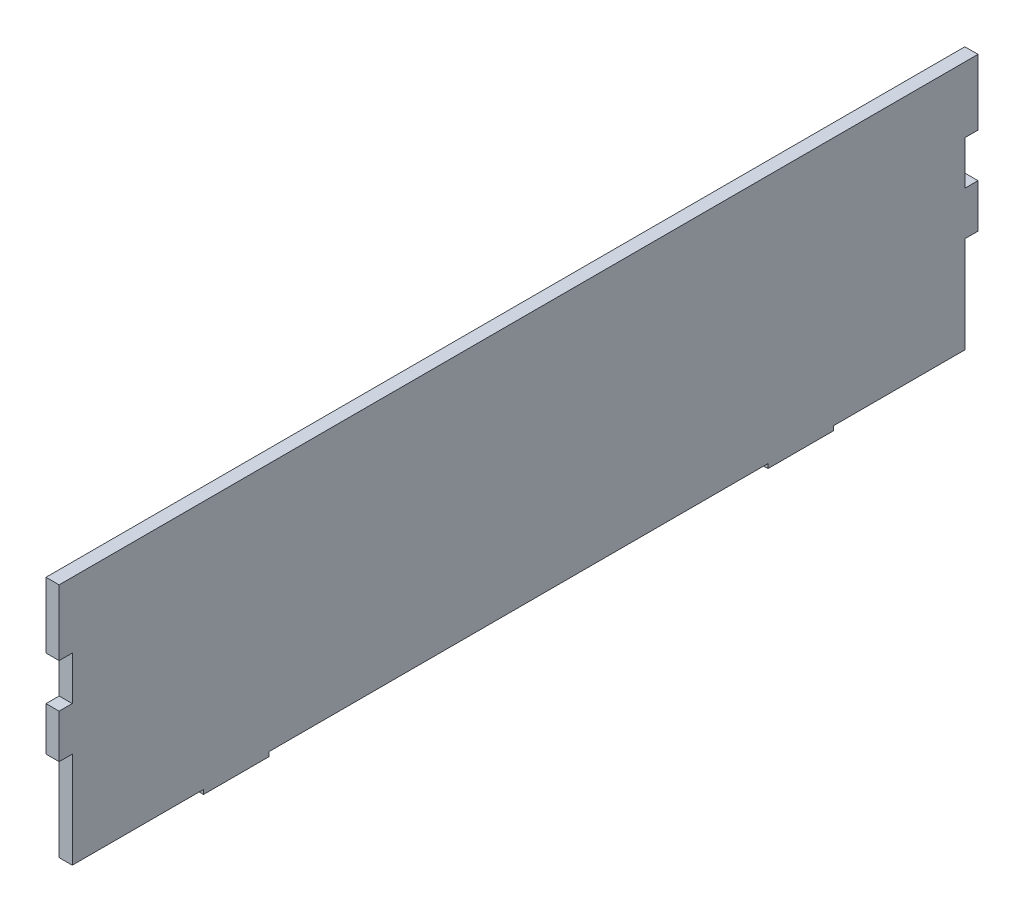
SolidWorks part; units mm, degrees
ref_plane "前视基准面" through (0, 0, 0) normal (0, 0, 1) x (1, 0, 0)
ref_plane "上视基准面" through (0, 0, 0) normal (0, 1, 0) x (1, 0, 0)
ref_plane "右视基准面" through (0, 0, 0) normal (1, 0, 0) x (0, 0, -1)
sketch "草图1" plane through (0, 0, 0) normal (0, 0, 1) x (1, 0, 0)
  line L0 (0, -1.0782) -> (0, -59.0782)
  line L1 (0, -59.0782) -> (150, -59.0782)
  line L3 (24.7207, -21.434) -> (24.7207, -1.0782)
  line L4 (24.7207, -1.0782) -> (0, -1.0782)
  line L5 (150, -59.0782) -> (150, -56.0782)
  line L6 (150, -56.0782) -> (24.7207, -21.434)
  dimension "D1" = 150
  dimension "D2" = 58
  dimension "D3" = 3
extrude "凸台-拉伸1" add sketch "草图1" along normal blind 0.5
sketch "草图2" plane through (0, 0, 0) normal (0, 0, -1) x (-1, 0, 0)
  line L0 (0, -1.0782) -> (-3, -1.0782)
  line L1 (-24.7207, -1.0782) -> (0, -1.0782) construction
  line L2 (-3, -1.0782) -> (-3, -54.0782)
  line L4 (-149.75, -59.0782) -> (0, -59.0782)
  line L5 (0, -59.0782) -> (0, -1.0782)
  line L6 (-150, -58.8282) -> (-150, -58.8207)
  line L7 (-149.7576, -58.5708) -> (-3, -54.0782)
  arc A0 (-150, -58.8207) -> (-149.7576, -58.5708) centre (-149.75, -58.8207) cw
  arc A1 (-150, -58.8282) -> (-149.75, -59.0782) centre (-149.75, -58.8282) ccw
  point P14 (-150, -58.5782)
  point P17 (-150, -59.0782)
  dimension "D3" = 0.25
  dimension "D1" = 5
  dimension "D2" = 0.5
extrude "凸台-拉伸2" add sketch "草图2" along normal blind 104.5
mirror "镜向3" about plane through (149.75, -58.8207, -104.5) normal (0, 0, 1) of bodies 102 106
sketch "草图8" plane through (-1.6511, -53.9358, 0) normal (0.0306, 0.9995, 0) x (0.9995, -0.0306, 0)
  line L0 (151.4797, 209) -> (151.4797, 0) construction
  line L1 (151.4797, 1) -> (91.4797, 1)
  line L2 (151.4797, 1) -> (151.4797, 9)
  line L3 (151.4797, 9) -> (91.4797, 9)
  line L4 (91.4797, 1) -> (91.4797, 9)
  line L5 (151.4797, 1) -> (91.4797, 9) construction
  line L6 (151.4797, 9) -> (91.4797, 1) construction
  line L7 (4.6533, 0) -> (151.4797, 0) construction
  line L8 (91.4737, 11) -> (151.4797, 11)
  line L9 (91.4737, 11) -> (91.4737, 19)
  line L10 (91.4737, 19) -> (151.4797, 19)
  line L11 (151.4797, 11) -> (151.4797, 19)
  line L12 (91.4737, 11) -> (151.4797, 19) construction
  line L13 (91.4737, 19) -> (151.4797, 11) construction
  line L14 (91.4737, 20.4211) -> (91.4737, 28.4211)
  line L15 (91.4737, 20.4211) -> (151.4797, 20.4211)
  line L16 (151.4797, 20.4211) -> (151.4797, 28.4211)
  line L17 (91.4737, 28.4211) -> (151.4797, 28.4211)
  line L18 (91.4737, 29.8421) -> (91.4737, 37.8421)
  line L19 (91.4737, 29.8421) -> (151.4797, 29.8421)
  line L20 (151.4797, 29.8421) -> (151.4797, 37.8421)
  line L21 (91.4737, 37.8421) -> (151.4797, 37.8421)
  line L22 (91.4737, 39.2632) -> (91.4737, 47.2632)
  line L23 (91.4737, 39.2632) -> (151.4797, 39.2632)
  line L24 (151.4797, 39.2632) -> (151.4797, 47.2632)
  line L25 (91.4737, 47.2632) -> (151.4797, 47.2632)
  line L26 (91.4737, 48.6842) -> (91.4737, 56.6842)
  line L27 (91.4737, 48.6842) -> (151.4797, 48.6842)
  line L28 (151.4797, 48.6842) -> (151.4797, 56.6842)
  line L29 (91.4737, 56.6842) -> (151.4797, 56.6842)
  line L30 (91.4737, 58.1053) -> (91.4737, 66.1053)
  line L31 (91.4737, 58.1053) -> (151.4797, 58.1053)
  line L32 (151.4797, 58.1053) -> (151.4797, 66.1053)
  line L33 (91.4737, 66.1053) -> (151.4797, 66.1053)
  line L34 (91.4737, 67.5263) -> (91.4737, 75.5263)
  line L35 (91.4737, 67.5263) -> (151.4797, 67.5263)
  line L36 (151.4797, 67.5263) -> (151.4797, 75.5263)
  line L37 (91.4737, 75.5263) -> (151.4797, 75.5263)
  line L38 (91.4737, 76.9474) -> (91.4737, 84.9474)
  line L39 (91.4737, 76.9474) -> (151.4797, 76.9474)
  line L40 (151.4797, 76.9474) -> (151.4797, 84.9474)
  line L41 (91.4737, 84.9474) -> (151.4797, 84.9474)
  line L42 (91.4737, 86.3684) -> (91.4737, 94.3684)
  line L43 (91.4737, 86.3684) -> (151.4797, 86.3684)
  line L44 (151.4797, 86.3684) -> (151.4797, 94.3684)
  line L45 (91.4737, 94.3684) -> (151.4797, 94.3684)
  line L46 (91.4737, 95.7895) -> (91.4737, 103.7895)
  line L47 (91.4737, 95.7895) -> (151.4797, 95.7895)
  line L48 (151.4797, 95.7895) -> (151.4797, 103.7895)
  line L49 (91.4737, 103.7895) -> (151.4797, 103.7895)
  line L50 (91.4737, 105.2105) -> (91.4737, 113.2105)
  line L51 (91.4737, 105.2105) -> (151.4797, 105.2105)
  line L52 (151.4797, 105.2105) -> (151.4797, 113.2105)
  line L53 (91.4737, 113.2105) -> (151.4797, 113.2105)
  line L54 (91.4737, 114.6316) -> (91.4737, 122.6316)
  line L55 (91.4737, 114.6316) -> (151.4797, 114.6316)
  line L56 (151.4797, 114.6316) -> (151.4797, 122.6316)
  line L57 (91.4737, 122.6316) -> (151.4797, 122.6316)
  line L58 (91.4737, 124.0526) -> (91.4737, 132.0526)
  line L59 (91.4737, 124.0526) -> (151.4797, 124.0526)
  line L60 (151.4797, 124.0526) -> (151.4797, 132.0526)
  line L61 (91.4737, 132.0526) -> (151.4797, 132.0526)
  line L62 (91.4737, 133.4737) -> (91.4737, 141.4737)
  line L63 (91.4737, 133.4737) -> (151.4797, 133.4737)
  line L64 (151.4797, 133.4737) -> (151.4797, 141.4737)
  line L65 (91.4737, 141.4737) -> (151.4797, 141.4737)
  line L66 (91.4737, 142.8947) -> (91.4737, 150.8947)
  line L67 (91.4737, 142.8947) -> (151.4797, 142.8947)
  line L68 (151.4797, 142.8947) -> (151.4797, 150.8947)
  line L69 (91.4737, 150.8947) -> (151.4797, 150.8947)
  line L70 (91.4737, 152.3158) -> (91.4737, 160.3158)
  line L71 (91.4737, 152.3158) -> (151.4797, 152.3158)
  line L72 (151.4797, 152.3158) -> (151.4797, 160.3158)
  line L73 (91.4737, 160.3158) -> (151.4797, 160.3158)
  line L74 (91.4737, 161.7368) -> (91.4737, 169.7368)
  line L75 (91.4737, 161.7368) -> (151.4797, 161.7368)
  line L76 (151.4797, 161.7368) -> (151.4797, 169.7368)
  line L77 (91.4737, 169.7368) -> (151.4797, 169.7368)
  line L78 (91.4737, 171.1579) -> (91.4737, 179.1579)
  line L79 (91.4737, 171.1579) -> (151.4797, 171.1579)
  line L80 (151.4797, 171.1579) -> (151.4797, 179.1579)
  line L81 (91.4737, 179.1579) -> (151.4797, 179.1579)
  line L82 (91.4737, 180.5789) -> (91.4737, 188.5789)
  line L83 (91.4737, 180.5789) -> (151.4797, 180.5789)
  line L84 (151.4797, 180.5789) -> (151.4797, 188.5789)
  line L85 (91.4737, 188.5789) -> (151.4797, 188.5789)
  line L86 (91.4737, 190) -> (91.4737, 198)
  line L87 (91.4737, 190) -> (151.4797, 190)
  line L88 (151.4797, 190) -> (151.4797, 198)
  line L89 (91.4737, 198) -> (151.4797, 198)
  line L90 (4.6533, 209) -> (151.4797, 209) construction
  line L91 (151.4797, 200) -> (91.4797, 200)
  line L92 (151.4797, 200) -> (151.4797, 208)
  line L93 (151.4797, 208) -> (91.4797, 208)
  line L94 (91.4797, 200) -> (91.4797, 208)
  line L95 (151.4797, 200) -> (91.4797, 208) construction
  line L96 (151.4797, 208) -> (91.4797, 200) construction
  point P4 (121.4797, 5)
  point P11 (121.4767, 15)
  point P94 (121.4797, 204)
  dimension "D1" = 60
  dimension "D2" = 8
  dimension "D3" = 8
  dimension "D4" = 2
  dimension "D5" = 1
  dimension "D7" = 8
  dimension "D8" = 2
  dimension "D9" = 60
  dimension "D10" = 1
  dimension "D6" = 20
extrude "切除-拉伸2" cut sketch "草图8" against normal blind 10
sketch "草图9" plane through (-1.6511, -53.9358, 0) normal (0.0306, 0.9995, 0) x (0.9995, -0.0306, 0)
  line L0 (151.6456, 209) -> (153.0857, 209)
  line L1 (151.4797, 1) -> (151.7162, 1)
  line L2 (151.4797, 1) -> (151.4797, 209)
  line L3 (151.4797, 209) -> (151.6456, 209)
  line L5 (153.0857, 209) -> (154.856, 1)
  line L6 (151.4797, 209) -> (151.7162, 1) construction
  line L7 (154.856, 1) -> (151.7162, 1)
  point P4 (151.5917, 110.4978)
extrude "切除-拉伸3" cut sketch "草图9" against normal blind 10
extrude "凸台-拉伸4" add sketch "草图1<3>" against normal blind 2.5
sketch "草图1<3>" plane through (0, 0, 0) normal (0, 0, 1) x (1, 0, 0) same geometry as "草图1"
fillet "圆角3" radius 0.25 22 edges at (149.7576, -58.5708, -170.4474) (149.7576, -58.5708, -179.8684) (149.7576, -58.5708, -189.2895) (149.7576, -58.5708, -199) (149.7576, -58.5708, -208.5) (149.7576, -58.5708, -85.6579) (149.7576, -58.5708, -95.0789) (149.7576, -58.5708, -104.5) (149.7576, -58.5708, -113.9211) (149.7576, -58.5708, -123.3421) (149.7576, -58.5708, -132.7632) (149.7576, -58.5708, -142.1842) (149.7576, -58.5708, -151.6053) (149.7576, -58.5708, -161.0263) (149.7576, -58.5708, -76.2368) (149.7576, -58.5708, -66.8158) (149.7576, -58.5708, -57.3947) (149.7576, -58.5708, -47.9737) (149.7576, -58.5708, -38.5526) (149.7576, -58.5708, -29.1316) (149.7576, -58.5708, -19.7105) (149.7576, -58.5708, -10)
fillet "圆角4" radius 0.25 22 edges at (149.7421, -59.0782, -47.9737) (149.7421, -59.0782, -38.5526) (149.7421, -59.0782, -29.1316) (149.7421, -59.0782, -19.7105) (149.7421, -59.0782, -10) (149.7421, -59.0782, -66.8158) (149.7421, -59.0782, -57.3947) (149.7421, -59.0782, -85.6579) (149.7421, -59.0782, -76.2368) (149.7421, -59.0782, -123.3421) (149.7421, -59.0782, -113.9211) (149.7421, -59.0782, -104.5) (149.7421, -59.0782, -95.0789) (149.7421, -59.0782, -132.7632) (149.7421, -59.0782, -142.1842) (149.7421, -59.0782, -151.6053) (149.7421, -59.0782, -161.0263) (149.7421, -59.0782, -208.5) (149.7421, -59.0782, -199) (149.7421, -59.0782, -189.2895) (149.7421, -59.0782, -179.8684) (149.7421, -59.0782, -170.4474)
sketch "草图10" plane through (0, 0, 0.5) normal (0, 0, 1) x (1, 0, 0)
  line L0 (0, -1.0782) -> (155.5397, -1.0782)
  line L1 (0, -1.0782) -> (0, -59.0782) construction
  line L2 (155.5397, -1.0782) -> (155.5397, -59.0782)
  line L3 (155.5397, -59.0782) -> (0, -59.0782)
  line L4 (0, -59.0782) -> (0, -1.0782)
ref_plane "基准面1" through (0, 0, -104.5) normal (0, 0, -1) x (-1, 0, 0)
mirror "镜向4" about plane through (0, 0, -104.5) normal (0, 0, -1) of "凸台-拉伸4"
sketch "草图7" plane through (0, 0, 0.5) normal (0, 0, 1) x (1, 0, 0)
  line L0 (0, -1.0782) -> (0, -59.0782) construction
  line L1 (8, -45.0782) -> (23, -45.0782) construction
  line L2 (0, -59.0782) -> (150, -59.0782) construction
  line L3 (23, -45.0782) -> (25, -45.0782) construction
  circle A0 centre (8, -45.0782) radius 3.5
  circle A1 centre (25, -45.0782) radius 0.5
  circle A2 centre (23, -45.0782) radius 0.5
  dimension "D1" = 8
  dimension "D3" = 17
  dimension "D4" = 2
  dimension "D2" = 14
extrude "切除-拉伸4" cut sketch "草图7" against normal blind 244
sketch "草图11" plane through (0, 0, 0.5) normal (0, 0, 1) x (1, 0, 0)
  line L1 (0, -59.0782) -> (182.234, -59.0782)
  line L2 (0, -59.0782) -> (0, 3.3635)
  line L3 (0, 3.3635) -> (182.234, 3.3635)
  line L4 (182.234, -59.0782) -> (182.234, 3.3635)
  line L5 (0, -59.0782) -> (182.234, 3.3635) construction
  line L6 (0, 3.3635) -> (182.234, -59.0782) construction
  point P4 (91.117, -27.8574)
extrude "切除-拉伸5" cut sketch "草图11" against normal blind 3
sketch "草图12" plane through (0, 0, -209.5) normal (0, 0, -1) x (-1, 0, 0)
  line L1 (0, -59.0782) -> (-153.3435, -59.0782)
  line L2 (0, -59.0782) -> (0, 7.254)
  line L3 (0, 7.254) -> (-153.3435, 7.254)
  line L4 (-153.3435, -59.0782) -> (-153.3435, 7.254)
  line L5 (0, -59.0782) -> (-153.3435, 7.254) construction
  line L6 (0, 7.254) -> (-153.3435, -59.0782) construction
  point P4 (-76.6718, -25.9121)
extrude "切除-拉伸6" cut sketch "草图12" against normal blind 3
sketch "草图13" plane through (3, 0, 0) normal (1, 0, 0) x (0, 0, -1)
  line L1 (2.5, -54.0782) -> (228.4191, -54.0782)
  line L2 (2.5, -54.0782) -> (2.5, -120.2498)
  line L3 (2.5, -120.2498) -> (228.4191, -120.2498)
  line L4 (228.4191, -54.0782) -> (228.4191, -120.2498)
  line L5 (2.5, -54.0782) -> (228.4191, -120.2498) construction
  line L6 (2.5, -120.2498) -> (228.4191, -54.0782) construction
  point P4 (115.4595, -87.164)
extrude "切除-拉伸7" cut sketch "草图13" along normal blind 164 and the other way blind 90 contours L2 L1 L4 L3
sketch "草图14" plane through (0, -54.0782, 0) normal (0, -1, 0) x (1, 0, 0)
  line L0 (3, -206.5) -> (3, -2.5) construction
  line L1 (3, -32.5) -> (0, -32.5)
  line L2 (3, -32.5) -> (3, -47.5)
  line L3 (3, -47.5) -> (0, -47.5)
  line L4 (0, -32.5) -> (0, -47.5)
  line L5 (3, -32.5) -> (0, -47.5) construction
  line L6 (3, -47.5) -> (0, -32.5) construction
  line L7 (0, -2.5) -> (0, -206.5) construction
  line L8 (0, -2.5) -> (3, -2.5) construction
  line L15 (3, -206.5) -> (0, -206.5) construction
  line L16 (3, -176.5) -> (0, -176.5)
  line L17 (3, -176.5) -> (3, -161.5)
  line L18 (3, -161.5) -> (0, -161.5)
  line L19 (0, -176.5) -> (0, -161.5)
  line L20 (3, -176.5) -> (0, -161.5) construction
  line L21 (3, -161.5) -> (0, -176.5) construction
  point P4 (1.5, -40)
  point P11 (1.5, -2.5)
  point P16 (1.5, -169)
  dimension "D1" = 30
  dimension "D2" = 15
  dimension "D3" = 15
  dimension "D4" = 30
extrude "凸台-拉伸5" add sketch "草图14" along normal blind 1
sketch "草图18" plane through (0, -1.0782, 0) normal (0, 1, 0) x (1, 0, 0)
  line L1 (3, 2.5) -> (0, 2.5)
  line L2 (3, 2.5) -> (3, 206.5)
  line L3 (3, 206.5) -> (0, 206.5)
  line L4 (0, 2.5) -> (0, 206.5)
  line L5 (3, 2.5) -> (0, 206.5) construction
  line L6 (3, 206.5) -> (0, 2.5) construction
  point P4 (1.5, 104.5)
extrude "凸台-拉伸6" add sketch "草图18" along normal blind 4
sketch "草图19" plane through (0, 0, -2.5) normal (0, 0, 1) x (1, 0, 0)
  line L0 (0, 2.9218) -> (0, -54.0782) construction
  line L1 (3, 2.9218) -> (0, 2.9218)
  line L2 (3, 2.9218) -> (3, -12.0782)
  line L3 (3, -12.0782) -> (0, -12.0782)
  line L4 (0, 2.9218) -> (0, -12.0782)
  line L5 (3, 2.9218) -> (0, -12.0782) construction
  line L6 (3, -12.0782) -> (0, 2.9218) construction
  line L7 (3, -54.0782) -> (3, 2.9218) construction
  line L8 (3, -22.0782) -> (0, -22.0782)
  line L9 (3, -22.0782) -> (3, -32.0782)
  line L10 (3, -32.0782) -> (0, -32.0782)
  line L11 (0, -22.0782) -> (0, -32.0782)
  line L12 (3, -22.0782) -> (0, -32.0782) construction
  line L13 (3, -32.0782) -> (0, -22.0782) construction
  point P4 (1.5, -4.5782)
  point P12 (1.5, -27.0782)
  point P15 (1.5, -12.0782)
  dimension "D1" = 15
  dimension "D2" = 10
  dimension "D3" = 10
extrude "凸台-拉伸7" add sketch "草图19" along normal blind 3
mirror "镜向5" about plane through (0, 0, -104.5) normal (0, 0, -1) of "凸台-拉伸7"
